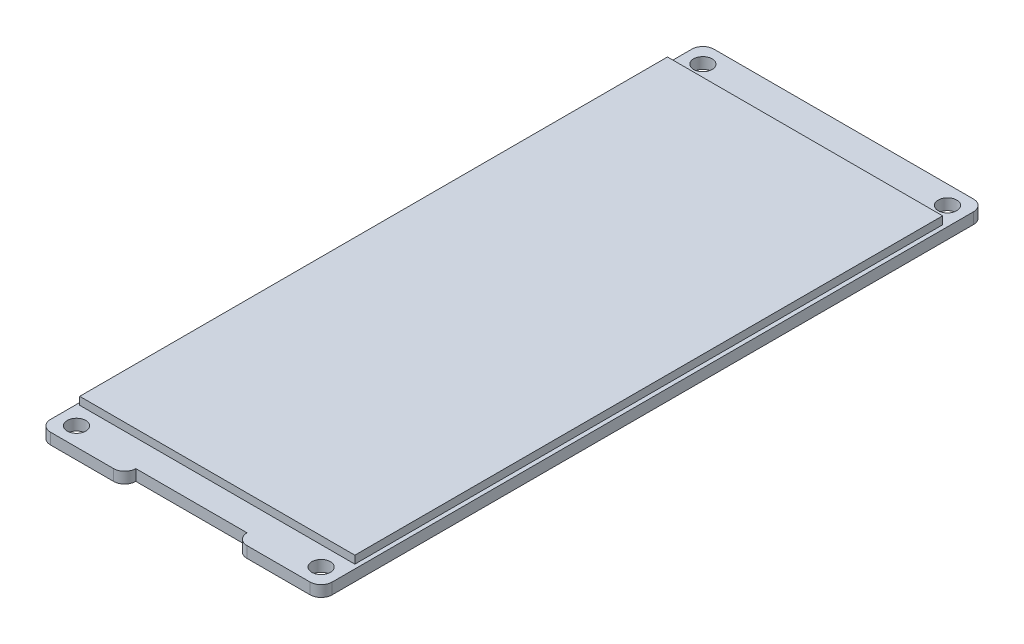
SolidWorks part; units mm, degrees
ref_plane "Front Plane" through (0, 0, 0) normal (0, 0, 1) x (1, 0, 0)
ref_plane "Top Plane" through (0, 0, 0) normal (0, 1, 0) x (1, 0, 0)
ref_plane "Right Plane" through (0, 0, 0) normal (1, 0, 0) x (0, 0, -1)
sketch "Sketch1" plane through (0, 0, 0) normal (0, 1, 0) x (1, 0, 0)
  line L1 (1.5, 0) -> (10, 0)
  line L2 (0, 1.5) -> (0, 88)
  line L3 (1.5, 89.5) -> (36.5, 89.5)
  line L4 (38, 1.5) -> (38, 88)
  line L5 (11.5, 1.5) -> (26.5, 1.5)
  line L7 (28, 0) -> (36.5, 0)
  arc A0 (36.5, 0) -> (38, 1.5) centre (36.5, 1.5) ccw
  arc A1 (1.5, 0) -> (0, 1.5) centre (1.5, 1.5) cw
  arc A2 (36.5, 89.5) -> (38, 88) centre (36.5, 88) cw
  arc A3 (0, 88) -> (1.5, 89.5) centre (1.5, 88) cw
  arc A4 (26.5, 1.5) -> (28, 0) centre (28, 1.5) ccw
  arc A5 (11.5, 1.5) -> (10, 0) centre (10, 1.5) cw
  circle A6 centre (2.5, 2.5) radius 1.25
  circle A7 centre (35.5, 2.5) radius 1.25
  circle A8 centre (35.5, 87) radius 1.25
  circle A9 centre (2.5, 87) radius 1.25
  point P7 (38, 0)
  point P10 (0, 0)
  point P13 (38, 89.5)
  point P16 (0, 89.5)
  point P25 (26.5, 0)
  dimension "D3" = 1.5
  dimension "D4" = 1.5
  dimension "D5" = 1.5
  dimension "D6" = 1.5
  dimension "D9" = 1.5
  dimension "D10" = 1.5
  dimension "D13" = 2.5
  dimension "D16" = 2.5
  dimension "D21" = 2.5
  dimension "D22" = 2.5
  dimension "D1" = 38
  dimension "D2" = 89.5
  dimension "D7" = 11.5
  dimension "D8" = 11.5
  dimension "D11" = 2.5
  dimension "D12" = 2.5
  dimension "D14" = 2.5
  dimension "D15" = 2.5
  dimension "D17" = 2.5
  dimension "D18" = 2.5
  dimension "D19" = 2.5
  dimension "D20" = 2.5
extrude "Boss-Extrude1" add sketch "Sketch1" along normal blind 1.5
sketch "Sketch2" plane through (0, 1.5, 0) normal (0, 1, 0) x (1, 0, 0)
  line L1 (0.3217, 5.1079) -> (37.4403, 5.1079)
  line L2 (0.3217, 5.1079) -> (0.3217, 84.4033)
  line L3 (0.3217, 84.4033) -> (37.4403, 84.4033)
  line L4 (37.4403, 5.1079) -> (37.4403, 84.4033)
extrude "Boss-Extrude2" add sketch "Sketch2" along normal blind 1.05
